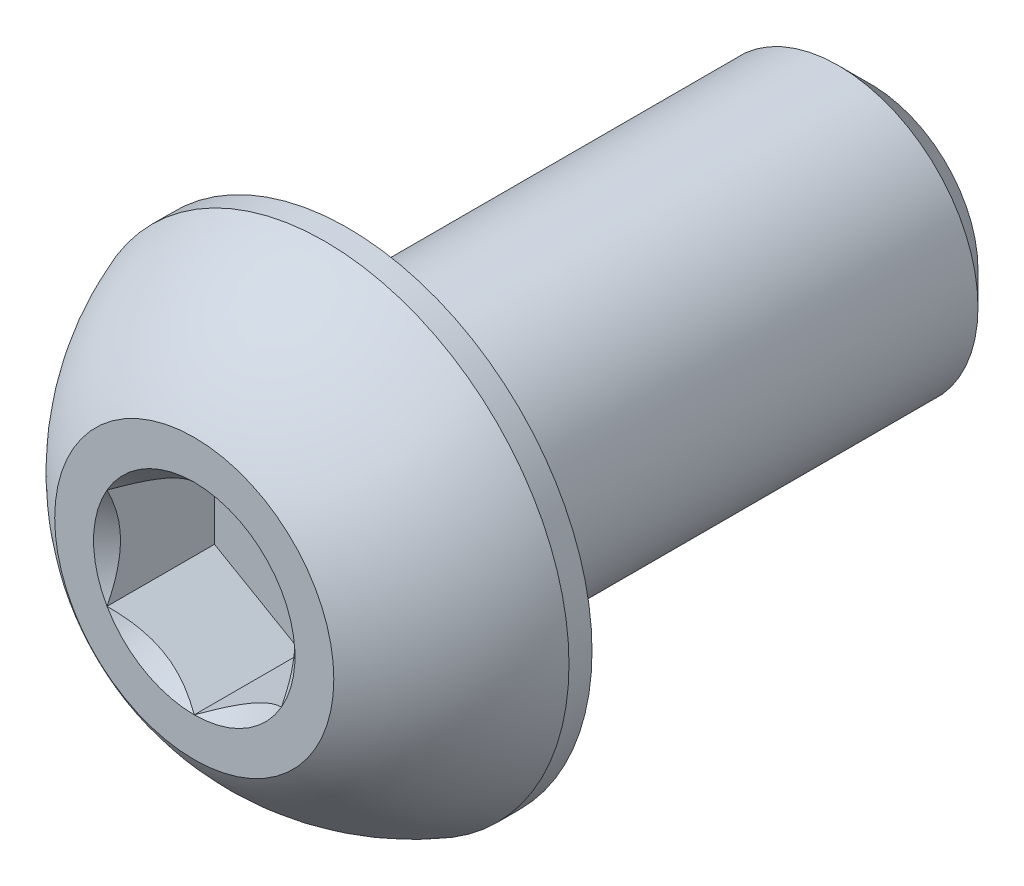
SolidWorks part; units mm, degrees
ref_plane "Front" through (0, 0, 0) normal (0, 0, 1) x (1, 0, 0)
ref_plane "Top" through (0, 0, 0) normal (0, 1, 0) x (1, 0, 0)
ref_plane "Right" through (0, 0, 0) normal (1, 0, 0) x (0, 0, -1)
sketch "Sketch1" plane through (0, 0, 0) normal (1, 0, 0) x (0, 0, -1)
  line L2 (4.4, 4) -> (19.4, 4)
  line L3 (19.4, 4) -> (19.4, 0)
  line L4 (19.4, 0) -> (4.4, 0)
  line L6 (3.74, 7) -> (4.4, 7) construction
  line L7 (19.4, 4) -> (19.4, -4) construction
  line L8 (0, 0) -> (4.4, 0) construction
  line L9 (4.4, 7) -> (4.4, -7) construction
  line L11 (4.4, 4) -> (4.4, 0)
  line L13 (0, 2.5) -> (0, -2.5) construction
  line L14 (0, 2.5) -> (0, 4) construction
  line L15 (19.3219, 4.1353) -> (19.9469, 3.0528) construction
  line L16 (19.9469, 3.0528) -> (20.5719, 4.1353) construction
  line L17 (20.5719, 4.1353) -> (19.3219, 4.1353) construction
  line L18 (19.4, 4) -> (20.4937, 4) construction
  line L19 (19.9469, 4.1353) -> (19.9469, 4) construction
  line L20 (19.9469, 4) -> (19.9469, 3.1881) construction
  line L21 (19.9469, 3.1881) -> (19.9469, 3.0528) construction
  line L22 (19.8687, 3.1881) -> (20.025, 3.1881)
  line L23 (19.3609, 4.0677) -> (20.5328, 4.0677)
  line L24 (20.025, 3.1881) -> (20.5328, 4.0677)
  line L25 (19.8687, 3.1881) -> (19.3609, 4.0677)
  line L26 (18.4625, 4) -> (19.4, 3.0625)
  arc A3 (0, 4) -> (3.74, 7) centre (6.2818, 0) cw construction
  point P29 (19.9469, 4.0677)
  point P30 (16.275, -4)
  dimension "D1" = 0.66
  dimension "Pitch" = 1.25
  dimension "D3" = 0.1562
  dimension "D2" = 0.9375
  dimension "D4" = 45
  dimension "D5" = 3.125
sketch "Sketch10" plane through (0, 0, 0) normal (1, 0, 0) x (0, 0, -1)
  line L0 (18.4625, 4) -> (19.4, 3.0625) construction
  line L1 (18.4625, 4) -> (19.4, 3.0625)
  line L4 (19.4, 4) -> (4.4, 4)
  line L5 (19.4, 0) -> (19.4, 4)
  line L6 (4.4, 0) -> (19.4, 0)
  line L7 (4.4, 4) -> (4.4, 0)
  line L8 (18.4625, 4) -> (4.4, 4)
  line L9 (19.4, 0) -> (19.4, 3.0625)
  line L10 (4.4, 0) -> (19.4, 0)
  line L11 (4.4, 4) -> (4.4, 0)
  dimension "D1" = 0
revolve "Revolve3" add sketch "Sketch10" angle 360 about L8
sketch "Sketch7" plane through (0, 0, 0) normal (1, 0, 0) x (0, 0, -1)
  line L6 (3.74, 7) -> (4.4, 7) construction
  line L8 (0, 0) -> (4.4, 0) construction
  line L11 (4.4, 7) -> (4.4, -7) construction
  line L12 (3.74, 7) -> (4.4, 7)
  line L13 (0, 0) -> (4.4, 0)
  line L14 (0, 2.5) -> (0, -2.5) construction
  line L15 (4.4, 7) -> (4.4, 0)
  line L16 (0, 4) -> (0, 0)
  arc A2 (3.74, 7) -> (0, 4) centre (6.2818, 0) ccw construction
  arc A3 (3.74, 7) -> (0, 4) centre (6.2818, 0) ccw
revolve "Revolve2" add sketch "Sketch7" angle 360 mid plane about L13
sketch "Sketch5" plane through (0, 0, 0) normal (0, 0, 1) x (1, 0, 0)
  line L1 (2.5, -1.4434) -> (2.5, 1.4434)
  line L2 (2.5, 1.4434) -> (0, 2.8868)
  line L3 (0, 2.8868) -> (-2.5, 1.4434)
  line L4 (-2.5, 1.4434) -> (-2.5, -1.4434)
  line L5 (-2.5, -1.4434) -> (0, -2.8868)
  line L6 (0, -2.8868) -> (2.5, -1.4434)
  circle A0 centre (0, 0) radius 2.5 construction
extrude "Cut-Extrude2" cut sketch "Sketch5" against normal blind 3.08
sketch "Sketch6" plane through (0, 0, 0) normal (0, 0, 1) x (1, 0, 0)
  circle A0 centre (0, 0) radius 2.8868
extrude "Cut-Extrude3" cut sketch "Sketch6" against normal blind 3.08 draft 45
sketch "Sketch9" [suppressed] plane through (0, 0, -4.4) normal (0, 0, -1) x (-1, 0, 0)
  circle A0 centre (0, 0) radius 4 construction
  circle A4 centre (0, 0) radius 4
split "Split1" [suppressed] bodies to split 113
sketch "Sketch11" [suppressed] plane through (0, 0, -19.4) normal (0, 0, -1) x (-1, 0, 0)
  circle A0 centre (0, 0) radius 4 construction
  circle A1 centre (0, 0) radius 4
curve "Helix/Spiral1" [suppressed] pitch 1.25 height 19.4 turns 15.52
sketch "Sketch12" [suppressed] plane through (0, 0, 0) normal (1, 0, 0) x (0, 0, -1)
  line L0 (19.8687, 3.1881) -> (20.025, 3.1881) construction
  line L1 (20.025, 3.1881) -> (20.5328, 4.0677) construction
  line L2 (19.3609, 4.0677) -> (20.5328, 4.0677) construction
  line L3 (19.8687, 3.1881) -> (19.3609, 4.0677) construction
  line L4 (19.8687, 3.1881) -> (20.025, 3.1881)
  line L5 (20.025, 3.1881) -> (20.5328, 4.0677)
  line L6 (19.3609, 4.0677) -> (20.5328, 4.0677)
  line L7 (19.8687, 3.1881) -> (19.3609, 4.0677)
sweep "Cut-Sweep2" [suppressed] cut profiles "Sketch12" path "Helix/Spiral1"
extrude "Boss-Extrude1" [suppressed] add sketch "Sketch9" along normal blind 10 draft 45
equation "\"D1@Cut-Extrude2\" = \"Head Ht@Sketch1\" * .7"
equation "\"D1@Sketch1\" = \"Head Ht@Sketch1\" * .15"
equation "\"D1@Cut-Extrude3\" = \"D1@Cut-Extrude2\""
equation "\"D3@Sketch1\" = \"Pitch@Sketch1\" / 8"
equation "\"D2@Sketch1\"=\"Pitch@Sketch1\"*0.75"
equation "\"D3@Helix/Spiral1\" = \"Lg@Sketch1\" + \"Head Ht@Sketch1\""
equation "\"D4@Helix/Spiral1\"=\"pitch@sketch1\""
equation "\"D5@Sketch1\"=\"Pitch@Sketch1\"*2.5"
